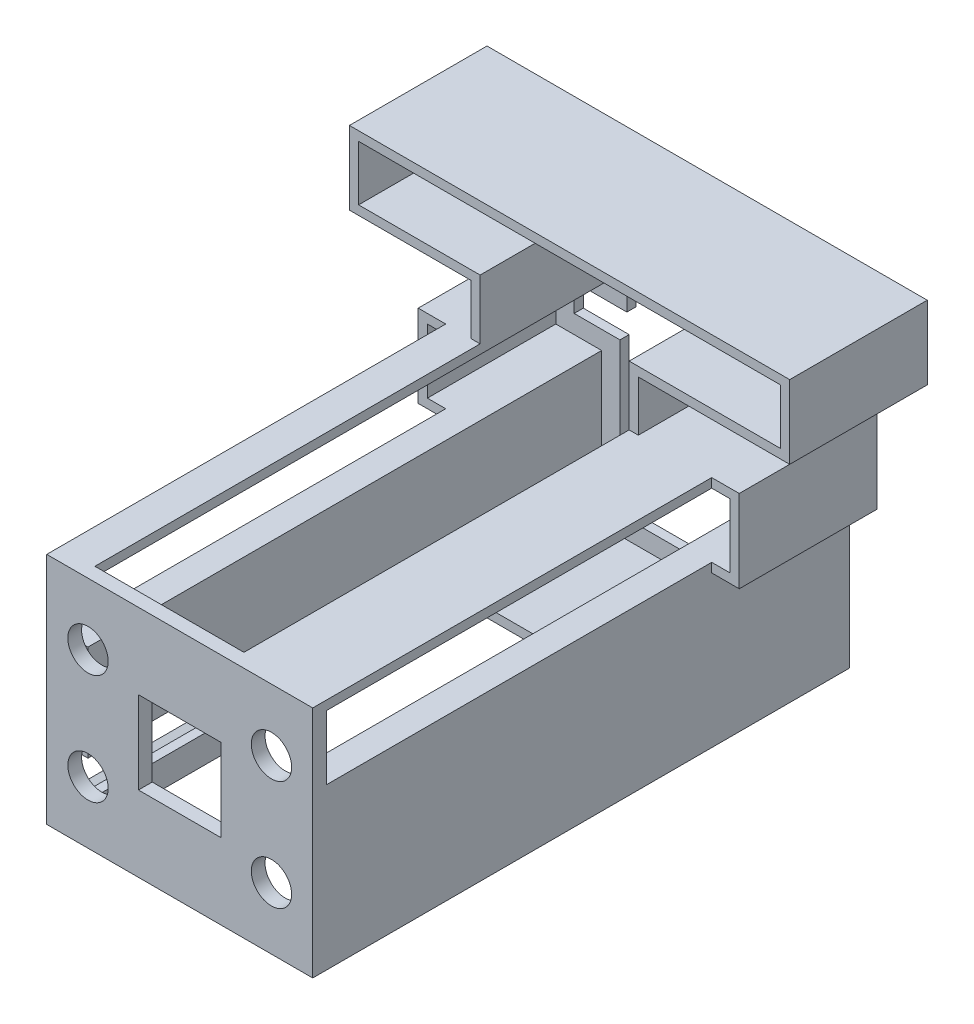
SolidWorks part; units mm, degrees
ref_plane "前视基准面" through (0, 0, 0) normal (0, 0, 1) x (1, 0, 0)
ref_plane "上视基准面" through (0, 0, 0) normal (0, 1, 0) x (1, 0, 0)
ref_plane "右视基准面" through (0, 0, 0) normal (1, 0, 0) x (0, 0, -1)
other "Configuration Table"
sketch "草图3" plane through (0, 0, 0) normal (0, 0, 1) x (1, 0, 0)
  line L0 (-4.5, 23.1299) -> (-4.5, -48.8588) construction
  line L1 (-11.5, 0) -> (11.5, 0)
  line L2 (-11.5, 0) -> (-11.5, -16.5)
  line L3 (-11.5, -16.5) -> (11.5, -16.5)
  line L4 (11.5, 0) -> (11.5, -16.5)
  line L5 (-16.5, 7) -> (16.5, 7)
  line L6 (-16.5, 7) -> (-16.5, 0)
  line L7 (-16.5, 0) -> (16.5, 0)
  line L8 (16.5, 7) -> (16.5, 0)
  line L9 (-10.75, 14.5) -> (5.5, 14.5)
  line L10 (-10.75, 14.5) -> (-10.75, 7)
  line L11 (-10.75, 7) -> (5.5, 7)
  line L12 (5.5, 14.5) -> (5.5, 7)
  line L13 (-25, 21.5) -> (23, 21.5)
  line L14 (-24, 20.5) -> (22, 20.5)
  line L15 (-24, 20.5) -> (-24, 14.5)
  line L16 (-24, 14.5) -> (22, 14.5)
  line L17 (22, 20.5) -> (22, 14.5)
  line L18 (23, 21.5) -> (23, 13.5)
  line L19 (-25, 13.5) -> (-11.75, 13.5)
  line L20 (-25, 21.5) -> (-25, 13.5)
  line L21 (-11.75, 13.5) -> (-11.75, 8)
  line L23 (6.5, 13.5) -> (6.5, 8)
  line L25 (-17.5, 8) -> (-11.75, 8)
  line L26 (17.5, 8) -> (17.5, -1)
  line L27 (-17.5, -1) -> (-12.5, -1)
  line L28 (-17.5, 8) -> (-17.5, -1)
  line L29 (12.5, -1) -> (12.5, -17.5)
  line L30 (-12.5, -17.5) -> (12.5, -17.5)
  line L31 (-12.5, -1) -> (-12.5, -17.5)
  line L33 (-11.75, 15.5) -> (6.5, 15.5) construction
  line L34 (6.5, 15.5) -> (6.5, 6) construction
  line L35 (-11.75, 15.5) -> (-11.75, 6) construction
  line L36 (6.5, 13.5) -> (23, 13.5)
  line L37 (-25, 13.5) -> (23, 13.5) construction
  line L38 (-12.5, 1) -> (12.5, 1) construction
  line L39 (6.5, 8) -> (17.5, 8)
  line L40 (-17.5, 8) -> (17.5, 8) construction
  line L41 (-11.75, 6) -> (6.5, 6) construction
  line L42 (-11.5, 0) -> (11.5, 0) construction
  line L43 (12.5, -1) -> (17.5, -1)
  line L44 (-17.5, -1) -> (17.5, -1) construction
  line L45 (12.5, 1) -> (12.5, -17.5) construction
  line L46 (-12.5, 1) -> (-12.5, -17.5) construction
  dimension "D1" = 23
  dimension "D2" = 16.5
  dimension "D3" = 7
  dimension "D4" = 33
  dimension "D5" = 12
  dimension "D6" = 6.25
  dimension "D7" = 7.5
  dimension "D8" = 10
  dimension "D9" = 46
  dimension "D10" = 19.5
  dimension "D11" = 6
  dimension "D12" = 1
extrude "凸台-拉伸1" add sketch "草图3" along normal blind 15 contours L31 L30 L29 L43 L26 L39 L23 L36 L18 L13 L20 L19 L21 L25 L28 L27
sketch "草图4" plane through (0, 0, 15) normal (0, 0, 1) x (1, 0, 0)
  line L0 (-25, 21.5) -> (-25, 13.5)
  line L1 (-25, 13.5) -> (-11.75, 13.5)
  line L2 (-11.75, 13.5) -> (-11.75, 8)
  line L3 (-11.75, 8) -> (-17.5, 8)
  line L4 (-17.5, 8) -> (-17.5, -1)
  line L5 (-17.5, -1) -> (-12.5, -1)
  line L6 (-12.5, -1) -> (-12.5, -17.5)
  line L7 (-12.5, -17.5) -> (12.5, -17.5)
  line L8 (12.5, -17.5) -> (12.5, -1)
  line L9 (12.5, -1) -> (17.5, -1)
  line L10 (17.5, -1) -> (17.5, 8)
  line L11 (17.5, 8) -> (6.5, 8)
  line L12 (6.5, 8) -> (6.5, 13.5)
  line L13 (6.5, 13.5) -> (23, 13.5)
  line L14 (23, 13.5) -> (23, 21.5)
  line L15 (23, 21.5) -> (-25, 21.5)
  line L16 (22, 20.5) -> (-24, 20.5)
  line L17 (-24, 20.5) -> (-24, 14.5)
  line L18 (-24, 14.5) -> (-10.75, 14.5)
  line L19 (-10.75, 14.5) -> (-10.75, 7)
  line L20 (-10.75, 7) -> (-16.5, 7)
  line L21 (-16.5, 7) -> (-16.5, 0)
  line L22 (-16.5, 0) -> (-11.5, 0)
  line L23 (-11.5, 0) -> (-11.5, -16.5)
  line L24 (-11.5, -16.5) -> (11.5, -16.5)
  line L25 (11.5, -16.5) -> (11.5, 0)
  line L26 (11.5, 0) -> (16.5, 0)
  line L27 (16.5, 0) -> (16.5, 7)
  line L28 (16.5, 7) -> (5.5, 7)
  line L29 (5.5, 7) -> (5.5, 14.5)
  line L30 (5.5, 14.5) -> (22, 14.5)
  line L31 (22, 14.5) -> (22, 20.5)
  dimension "D1" = 1
extrude "切除-拉伸1" cut sketch "草图4" against normal blind 14 contours L16 L17 L18 L19 L20 L21 L22 L23 L24 L25 L26 L27 L28 L29 L30 L31
sketch "草图7" plane through (0, 0, 1) normal (0, 0, 1) x (1, 0, 0)
  line L0 (-24, 20.5) -> (-24, 14.5)
  line L1 (-24, 20.5) -> (-24, 14.5) construction
  line L2 (-24, 14.5) -> (22, 14.5)
  line L3 (22, 14.5) -> (22, 20.5)
  line L4 (22, 20.5) -> (-24, 20.5)
extrude "切除-拉伸2" cut sketch "草图7" against normal up to surface (1 mm away) contours L4 L0 L2 L3 up to face at (-0.9063, 5.625, 0)
sketch "草图8" plane through (-12.5, 0, 0) normal (-1, 0, 0) x (0, 0, 1)
  line L1 (1, -10.5) -> (15, -10.5)
  line L2 (1, -10.5) -> (1, -14.5)
  line L3 (1, -14.5) -> (15, -14.5)
  line L4 (15, -10.5) -> (15, -14.5)
  line L5 (15, -1) -> (15, -17.5) construction
  line L6 (15, -17.5) -> (0, -17.5) construction
  line L7 (0, -1) -> (0, -17.5) construction
  dimension "D1" = 3
  dimension "D2" = 7
  dimension "D3" = 1
extrude "切除-拉伸3" cut sketch "草图8" against normal up to surface (1 mm away) contours L2 L1 L4 L3 up to face at (-11.5, -8.25, 8)
sketch "草图9" plane through (0, 0, 0) normal (0, 0, -1) x (-1, 0, 0)
  line L0 (-6.5, 13.5) -> (-6.5, 8)
  line L1 (-6.5, 8) -> (-17.5, 8)
  line L2 (-17.5, 8) -> (-17.5, -1)
  line L3 (-17.5, -1) -> (-12.5, -1)
  line L4 (-12.5, -1) -> (-12.5, -17.5)
  line L5 (-12.5, -17.5) -> (12.5, -17.5)
  line L6 (12.5, -17.5) -> (12.5, -1)
  line L7 (12.5, -1) -> (17.5, -1)
  line L8 (17.5, -1) -> (17.5, 8)
  line L9 (17.5, 8) -> (11.75, 8)
  line L10 (11.75, 8) -> (11.75, 14.5)
  line L11 (24, 14.5) -> (-22, 14.5) construction
  line L12 (11.75, 14.5) -> (-6.5, 14.5)
  line L13 (-6.5, 14.5) -> (-6.5, 13.5)
  line L14 (-3.5, 11.5) -> (-3.5, 11.5)
  line L15 (-3.5, 11.5) -> (-3.5, 5)
  line L16 (-3.5, 5) -> (-14.5, 5)
  line L17 (-14.5, 5) -> (-14.5, 2)
  line L18 (-14.5, 2) -> (-9.5, 2)
  line L19 (-9.5, 2) -> (-9.5, -14.5)
  line L20 (-9.5, -14.5) -> (9.5, -14.5)
  line L21 (9.5, -14.5) -> (9.5, 2)
  line L22 (9.5, 2) -> (14.5, 2)
  line L23 (14.5, 2) -> (14.5, 5)
  line L24 (14.5, 5) -> (8.75, 5)
  line L25 (8.75, 5) -> (8.75, 11.5)
  line L26 (8.75, 11.5) -> (-3.5, 11.5)
  dimension "D1" = 3
extrude "切除-拉伸6" cut sketch "草图9" against normal up to surface (1 mm away) contours L25 L26 L15 L16 L17 L18 L19 L20 L21 L22 L23 L24 region at (-0.4353, -2.0786, 0) up to face at (-3.6562, -1.625, 1)
sketch "草图24" plane through (0, 0, 0) normal (0, 0, -1) x (-1, 0, 0)
  line L0 (-12.5, -17.5) -> (-14.5, -17.5)
  line L1 (-14.5, -17.5) -> (-14.5, -15.5)
  line L3 (-12.5, -16.5) -> (-12.5, -17.5)
  line L4 (12.5, -17.5) -> (14.5, -17.5)
  line L5 (14.5, -17.5) -> (14.5, -15.5)
  line L7 (12.5, -15.5) -> (12.5, -17.5)
  line L8 (-14.5, -15.5) -> (-12.5, -14.5)
  line L13 (12.5, -1) -> (14.5, -1)
  line L16 (12.5, -1) -> (17.5, -1)
  line L17 (17.5, -1) -> (17.5, 8)
  line L18 (17.5, 8) -> (11.75, 8)
  line L19 (11.75, 8) -> (11.75, 13.5)
  line L20 (11.75, 13.5) -> (25, 13.5)
  line L21 (25, 13.5) -> (25, 21.5)
  line L22 (25, 21.5) -> (-23, 21.5)
  line L23 (-23, 21.5) -> (-23, 13.5)
  line L24 (-23, 13.5) -> (-6.5, 13.5)
  line L25 (-6.5, 13.5) -> (-6.5, 8)
  line L26 (-6.5, 8) -> (-17.5, 8)
  line L27 (-17.5, 8) -> (-17.5, -1)
  line L28 (-17.5, -1) -> (-12.5, -1)
  line L29 (-12.5, -1) -> (-12.5, -17.5)
  line L30 (-12.5, -17.5) -> (12.5, -17.5)
  line L31 (12.5, -17.5) -> (12.5, -1)
  line L32 (12.5, -1) -> (17.5, -1)
  line L33 (17.5, -1) -> (17.5, 8)
  line L34 (17.5, 8) -> (11.75, 8)
  line L35 (11.75, 8) -> (11.75, 13.5)
  line L36 (11.75, 13.5) -> (25, 13.5)
  line L37 (25, 13.5) -> (25, 21.5)
  line L38 (25, 21.5) -> (-23, 21.5)
  line L39 (-23, 21.5) -> (-23, 13.5)
  line L40 (-23, 13.5) -> (-6.5, 13.5)
  line L41 (-6.5, 13.5) -> (-6.5, 8)
  line L42 (-6.5, 8) -> (-17.5, 8)
  line L43 (-17.5, 8) -> (-17.5, -1)
  line L44 (-17.5, -1) -> (-12.5, -1)
  line L45 (-12.5, -1) -> (-12.5, -17.5)
  line L46 (-12.5, -17.5) -> (12.5, -17.5)
  line L47 (12.5, -17.5) -> (12.5, -1)
  line L48 (-14.5, 8) -> (-12.5, 8)
  line L49 (-14.5, 8) -> (-14.5, 7)
  line L50 (-14.5, 7) -> (-12.5, 7)
  line L51 (-12.5, 8) -> (-12.5, 7)
  line L52 (12.5, 8) -> (14.5, 8)
  line L53 (12.5, 8) -> (12.5, 7)
  line L54 (12.5, 7) -> (14.5, 7)
  line L55 (14.5, 8) -> (14.5, 7)
  line L56 (14.5, -15.5) -> (12.5, -14.5)
  line L57 (-12.5, -14.5) -> (12.5, -14.5) construction
  line L58 (-14.5, -15.5) -> (14.5, -15.5) construction
  line L59 (12.5, 8) -> (10.75, 8)
  line L60 (12.5, 0) -> (14.5, 0)
  line L61 (12.5, 0) -> (12.5, -10.5)
  line L62 (12.5, -10.5) -> (14.5, -10.5)
  line L63 (14.5, 0) -> (14.5, -10.5)
  line L64 (-14.5, 0) -> (-12.5, 0)
  line L65 (-14.5, 0) -> (-14.5, -15.5)
  line L66 (-14.5, -15.5) -> (-12.5, -15.5)
  line L67 (-12.5, 0) -> (-12.5, -15.5)
  line L68 (-12.5, 0) -> (-11.5, 0)
  line L69 (-12.5, 0) -> (-12.5, -17.5)
  line L70 (-12.5, -17.5) -> (-11.5, -17.5)
  line L71 (-11.5, 0) -> (-11.5, -17.5)
  line L72 (11.5, 0) -> (12.5, 0)
  line L73 (11.5, 0) -> (11.5, -10.5)
  line L74 (11.5, -10.5) -> (12.5, -10.5)
  line L75 (12.5, 0) -> (12.5, -10.5)
  line L76 (11.5, -14.5) -> (12.5, -14.5)
  line L77 (11.5, -14.5) -> (11.5, -17.5)
  line L78 (11.5, -17.5) -> (12.5, -17.5)
  line L79 (12.5, -14.5) -> (12.5, -17.5)
  line L80 (10.75, 8) -> (10.75, 7)
  line L81 (12.5, 7) -> (12.5, 8)
  line L82 (-12.5, 8) -> (-5.5, 8)
  line L83 (-5.5, 8) -> (-5.5, 7)
  line L84 (-12.5, 7) -> (-5.5, 7)
  line L85 (-12.5, 8) -> (-12.5, 7)
  line L86 (10.75, 8) -> (12.5, 8)
  line L87 (12.5, 8) -> (12.5, 7)
  line L88 (12.5, 7) -> (10.75, 7)
  line L89 (10.75, 7) -> (10.75, 8)
  line L93 (11.5, -10.5) -> (12.5, -10.5)
  line L94 (11.5, 0) -> (11.5, -10.5)
  line L95 (16.5, 0) -> (11.5, 0)
  line L96 (16.5, 7) -> (16.5, 0)
  line L97 (10.75, 7) -> (16.5, 7)
  line L98 (10.75, 14.5) -> (10.75, 7)
  line L99 (24, 14.5) -> (10.75, 14.5)
  line L100 (24, 20.5) -> (24, 14.5)
  line L101 (-22, 20.5) -> (24, 20.5)
  line L102 (-22, 14.5) -> (-22, 20.5)
  line L103 (-5.5, 14.5) -> (-22, 14.5)
  line L104 (-5.5, 7) -> (-5.5, 14.5)
  line L105 (-16.5, 7) -> (-5.5, 7)
  line L106 (-16.5, 0) -> (-16.5, 7)
  line L107 (-11.5, 0) -> (-16.5, 0)
  line L108 (-11.5, -16.5) -> (-11.5, 0)
  line L109 (11.5, -16.5) -> (-11.5, -16.5)
  line L110 (11.5, -14.5) -> (11.5, -16.5)
  line L111 (12.5, -14.5) -> (11.5, -14.5)
  line L112 (12.5, -17.5) -> (12.5, -14.5)
  line L113 (-12.5, -17.5) -> (12.5, -17.5)
  line L114 (-12.5, -1) -> (-12.5, -17.5)
  line L115 (-17.5, -1) -> (-12.5, -1)
  line L116 (-17.5, 8) -> (-17.5, -1)
  line L117 (-6.5, 8) -> (-17.5, 8)
  line L118 (-6.5, 13.5) -> (-6.5, 8)
  line L119 (-23, 13.5) -> (-6.5, 13.5)
  line L120 (-23, 21.5) -> (-23, 13.5)
  line L121 (25, 21.5) -> (-23, 21.5)
  line L122 (25, 13.5) -> (25, 21.5)
  line L123 (11.75, 13.5) -> (25, 13.5)
  line L124 (11.75, 8) -> (11.75, 13.5)
  line L125 (17.5, 8) -> (11.75, 8)
  line L126 (17.5, -1) -> (17.5, 8)
  line L127 (12.5, -1) -> (17.5, -1)
  line L128 (12.5, -10.5) -> (12.5, -1)
  line L129 (11.5, -10.5) -> (12.5, -10.5)
  line L130 (11.5, 0) -> (11.5, -10.5)
  line L131 (16.5, 0) -> (11.5, 0)
  line L132 (16.5, 7) -> (16.5, 0)
  line L133 (10.75, 7) -> (16.5, 7)
  line L134 (10.75, 14.5) -> (10.75, 7)
  line L135 (24, 14.5) -> (10.75, 14.5)
  line L136 (24, 20.5) -> (24, 14.5)
  line L137 (-22, 20.5) -> (24, 20.5)
  line L138 (-22, 14.5) -> (-22, 20.5)
  line L139 (-5.5, 14.5) -> (-22, 14.5)
  line L140 (-5.5, 7) -> (-5.5, 14.5)
  line L141 (-16.5, 7) -> (-5.5, 7)
  line L142 (-16.5, 0) -> (-16.5, 7)
  line L143 (-11.5, 0) -> (-16.5, 0)
  line L144 (-11.5, -16.5) -> (-11.5, 0)
  line L145 (11.5, -16.5) -> (-11.5, -16.5)
  line L146 (11.5, -14.5) -> (11.5, -16.5)
  line L147 (12.5, -14.5) -> (11.5, -14.5)
  line L148 (12.5, -17.5) -> (12.5, -14.5)
  line L149 (-12.5, -17.5) -> (12.5, -17.5)
  line L150 (-12.5, -1) -> (-12.5, -17.5)
  line L151 (-17.5, -1) -> (-12.5, -1)
  line L152 (-17.5, 8) -> (-17.5, -1)
  line L153 (-6.5, 8) -> (-17.5, 8)
  line L154 (-6.5, 13.5) -> (-6.5, 8)
  line L155 (-23, 13.5) -> (-6.5, 13.5)
  line L156 (-23, 21.5) -> (-23, 13.5)
  line L157 (25, 21.5) -> (-23, 21.5)
  line L158 (25, 13.5) -> (25, 21.5)
  line L159 (11.75, 13.5) -> (25, 13.5)
  line L160 (11.75, 8) -> (11.75, 13.5)
  line L161 (17.5, 8) -> (11.75, 8)
  line L162 (17.5, -1) -> (17.5, 8)
  line L163 (12.5, -1) -> (17.5, -1)
  line L164 (12.5, -10.5) -> (12.5, -1)
  line M41 (12.5, -1) -> (17.5, -1)
  line M51 (-6.5, 8) -> (-17.5, 8)
  line M54 (-12.5, -1) -> (-12.5, -17.5)
  line M55 (-12.5, -17.5) -> (12.5, -17.5)
  line M56 (12.5, -17.5) -> (12.5, -1)
  dimension "D2" = 2
  dimension "D3" = 0
  dimension "D4" = 2
  dimension "D5" = 2
  dimension "D6" = 1
  dimension "D7" = 2
  dimension "D1" = 0
extrude "凸台-拉伸10" add sketch "草图24" against normal blind 57 contours L1 L0 M54 | L5 L4 M56 | L55 L34 L53 L54 | L51 L42 L49 L50 | L63 L62 M41 M56 | L71 L68 L67 L45 M54 M55 | L73 L74 L61 L72 M56 | L76 L77 M55 M56 | L63 L60 L61 M41 | L51 L84 L83 L82 M51 | L66 L67 L64 L65 region at (13.5, -16.5, 0) region at (12, -8.75, 0) region at (-12, -16, 0) region at (-13.4333, -16.2333, 0) region at (13.5, 7.5, 0) region at (-12, -5.25, 0) region at (-13.5, -5.75, 0) region at (9, 7.5, 0) region at (-13.5, -0.5, 0) region at (-13.5, 7.5, 0)
sketch "草图29" plane through (0, 0, 57) normal (0, 0, 1) x (1, 0, 0)
  line L1 (-14.5, -17.5) -> (14.5, -17.5)
  line L2 (-14.5, -17.5) -> (-14.5, 8)
  line L3 (-14.5, 8) -> (14.5, 8)
  line L4 (14.5, -17.5) -> (14.5, 8)
extrude "凸台-拉伸12" add sketch "草图29" along normal blind 1.5 contours L2 L1 L4 L3
sketch "草图30" plane through (0, 0, 58.5) normal (0, 0, 1) x (1, 0, 0)
  line L0 (-10, 1.25) -> (10, 1.25) construction
  line L1 (-14.5, 8) -> (14.5, 8) construction
  line L2 (0, 8) -> (0, -1.1394) construction
  line L3 (-10, -10.75) -> (-10, 1.25) construction
  line L4 (-10, -4.75) -> (-6.3218, -4.75) construction
  line L5 (-14.5, -17.5) -> (-14.5, 8) construction
  line L7 (-4.5, -0.25) -> (4.5, -0.25)
  line L8 (-4.5, -0.25) -> (-4.5, -9.25)
  line L9 (-4.5, -9.25) -> (4.5, -9.25)
  line L10 (4.5, -0.25) -> (4.5, -9.25)
  line L11 (-4.5, -0.25) -> (4.5, -9.25) construction
  line L12 (-4.5, -9.25) -> (4.5, -0.25) construction
  circle A0 centre (-10, 1.25) radius 2.2
  circle A1 centre (10, 1.25) radius 2.2
  circle A2 centre (10, -10.75) radius 2.2
  circle A3 centre (-10, -10.75) radius 2.2
  point P2 (0, 8)
  point P12 (0, 1.25)
  point P15 (-10, -4.75)
  point P17 (-14.5, -4.75)
  point P19 (-10, -4.75)
  point P22 (0, -4.75)
  dimension "D3" = 4.4
  dimension "D4" = 20
  dimension "D5" = 12
  dimension "D6" = 9
  dimension "D7" = 9
  dimension "D1" = 2
  dimension "D2" = 2
extrude "切除-拉伸8" cut sketch "草图30" against normal up to surface (1.5 mm away) contours A0 | A3 | A1 | A2 | L10 L7 L8 L9 region at (0, -4.75, 58.5) region at (-10, 1.25, 58.5) region at (10, 1.25, 58.5) region at (10, -10.75, 58.5) region at (-10, -10.75, 58.5) up to face at (-4.6176, -3.3235, 57)
sketch "草图31" plane through (0, 0, 15) normal (0, 0, 1) x (1, 0, 0)
  line L1 (-12.5, 8) -> (-10.75, 8)
  line L2 (-12.5, 8) -> (-12.5, 7)
  line L3 (-12.5, 7) -> (-10.75, 7)
  line L4 (-10.75, 8) -> (-10.75, 7)
extrude "凸台-拉伸13" add sketch "草图31" along normal up to surface (42 mm away) contours L2 L1 L4 L3 up to face at (-3.0718, -3.8202, 57)
